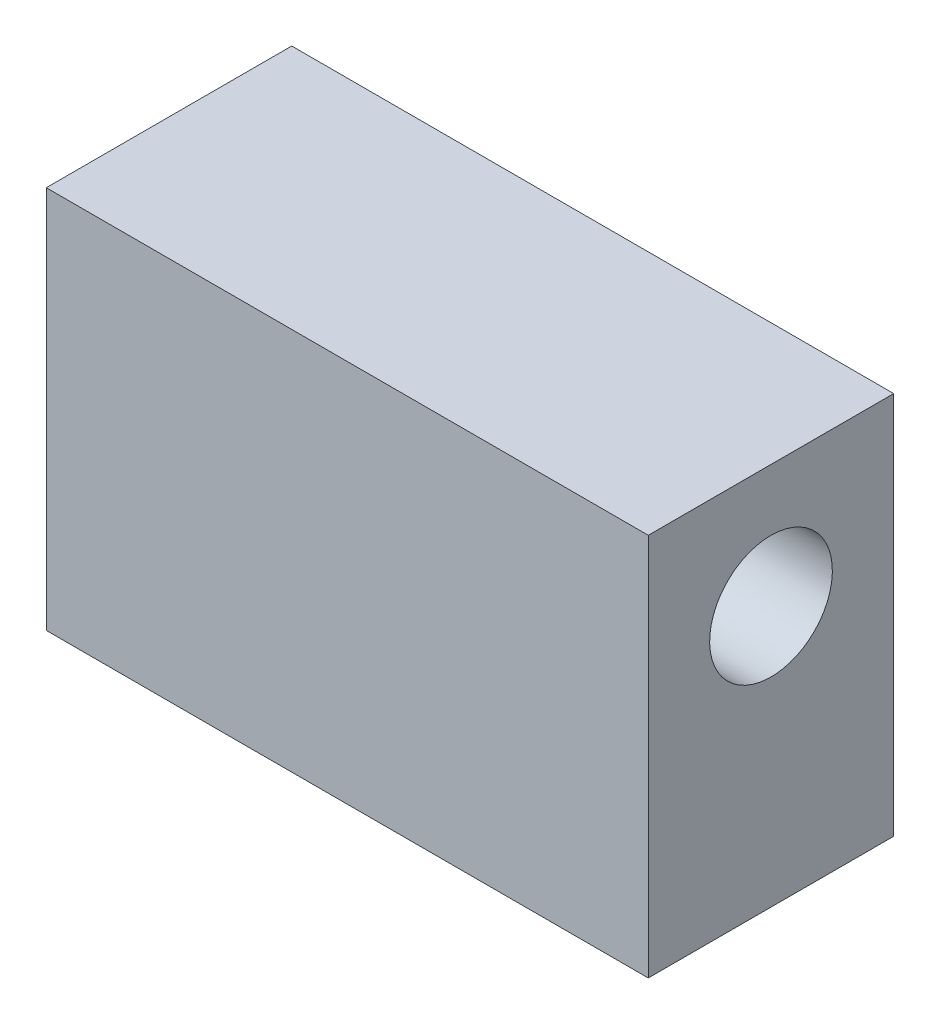
SolidWorks part; units mm, degrees
material "1060 Alloy"
ref_plane "Front" through (0, 0, 0) normal (0, 0, 1) x (1, 0, 0)
ref_plane "Top" through (0, 0, 0) normal (0, 1, 0) x (1, 0, 0)
ref_plane "Right" through (0, 0, 0) normal (1, 0, 0) x (0, 0, -1)
sketch "Sketch3" plane through (0, 0, 0) normal (0, 0, 1) x (1, 0, 0)
  line L0 (-0.127, -6.35) -> (30.1755, -6.35)
  line L1 (0, 0) -> (31.1484, 0)
  line L2 (0, 0) -> (0, -19.8376)
  line L3 (0, -19.8376) -> (31.1484, -19.8376)
  line L4 (31.1484, 0) -> (31.1484, -19.8376)
  line L5 (15.5742, -19.8376) -> (15.5742, 0) construction
  line L6 (15.5742, -6.35) -> (8.0621, -19.3614) construction
  line L15 (12.5496, -11.5887) -> (15.5742, -13.335) construction
  line L16 (15.5742, -6.35) -> (22.9274, -19.0862) construction
  circle A0 centre (15.5742, -6.35) radius 6.0492 construction
  point P14 (0, -6.35)
  point P17 (9.525, -6.35)
  point P19 (31.1484, -6.35)
  point P20 (7.7871, -19.8376)
  point P24 (23.3613, -19.8376)
  dimension "D2" = 6.35
  dimension "D6" = 3.4925
  dimension "D3" = 60
  dimension "D1" = 9.525
  dimension "D4" = 9.525
  dimension "D5" = 60
extrude "Boss-Extrude1" add sketch "Sketch3" along normal mid plane 12.7
sketch "Sketch4" plane through (0, 0, 0) normal (-1, 0, 0) x (0, 0, 1)
  circle A0 centre (0, -6.35) radius 3.175
  dimension "D1" = 6.35
extrude "Cut-Extrude1" cut sketch "Sketch4" against normal blind 9.525
ref_plane "Plane1" through (7.7871, -19.8376, 0) normal (-0.5, -0.866, 0) x (-0.866, 0.5, 0)
ref_plane "Mirror Plane" through (15.5742, 0, 0) normal (-1, 0, 0) x (0, 0, 1)
sketch "Sketch5" plane through (7.7871, -19.8376, 0) normal (-0.5, -0.866, 0) x (-0.866, 0.5, 0)
  circle A0 centre (0, 0) radius 3.175
  dimension "D1" = 6.35
extrude "Cut-Extrude5" cut sketch "Sketch5" against normal blind 9.525 and the other way up to next
sketch "Sketch6" plane through (0, 0, -6.35) normal (0, 0, -1) x (-1, 0, 0)
  circle A0 centre (-15.5742, -6.35) radius 3.175
  dimension "D1" = 6.35
extrude "Cut-Extrude6" cut sketch "Sketch6" against normal blind 9.525
mirror "Mirror1" about plane through (15.5742, 0, 0) normal (-1, 0, 0) of "Cut-Extrude1", "Cut-Extrude5"
equation "\"truss_member_od\" = .25in"
equation "\"truss_member_id\"= 0in"
equation "\"truss_member_L1\" = 2.125in"
equation "\"connector_hole_depth\" = .375in"
equation "\"D1@Boss-Extrude1\"=\"truss_member_od\"*2"
equation "\"D6@Sketch3\"=\"truss_member_od\"/2*1.1"
equation "\"D1@Sketch4\"=\"truss_member_od\""
equation "\"D1@Cut-Extrude1\"=\"connector_hole_depth\""
equation "\"D1@Sketch3\"=\"connector_hole_depth\""
equation "\"D4@Sketch3\"=\"connector_hole_depth\""
equation "\"D1@Sketch5\"=\"truss_member_od\""
equation "\"D1@Cut-Extrude5\"=\"connector_hole_depth\""
equation "\"D1@Cut-Extrude6\"=\"connector_hole_depth\""
equation "\"D1@Sketch6\"=\"truss_member_od\""
